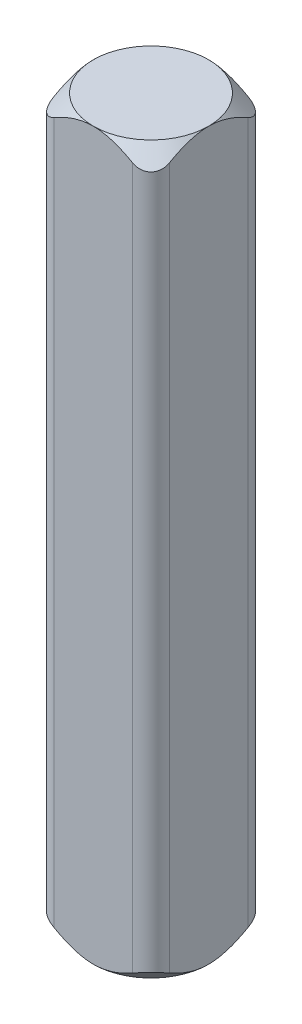
SolidWorks part; units mm, degrees
material "Plain Carbon Steel"
ref_plane "Front Plane" through (0, 0, 0) normal (0, 0, 1) x (1, 0, 0)
ref_plane "Top Plane" through (0, 0, 0) normal (0, 1, 0) x (1, 0, 0)
ref_plane "Right Plane" through (0, 0, 0) normal (1, 0, 0) x (0, 0, -1)
sketch "Sketch1" plane through (0, 0, 0) normal (0, 1, 0) x (1, 0, 0)
  line L1 (-1.5875, -1.5875) -> (1.5875, -1.5875)
  line L2 (-1.5875, -1.5875) -> (-1.5875, 1.5875)
  line L3 (-1.5875, 1.5875) -> (1.5875, 1.5875)
  line L4 (1.5875, -1.5875) -> (1.5875, 1.5875)
  line L5 (-1.5875, -1.5875) -> (1.5875, 1.5875) construction
  line L6 (-1.5875, 1.5875) -> (1.5875, -1.5875) construction
  point P0 (0, 0)
  dimension "D1" = 3.175
extrude "Boss-Extrude1" add sketch "Sketch1" along normal mid plane 20
ref_axis "a" through (0, 12.013, 0) along (0, -1, 0)
fillet "Fillet1" radius 0.508 4 edges at (-1.5875, 0, -1.5875) (-1.5875, 0, 1.5875) (1.5875, 0, -1.5875) (1.5875, 0, 1.5875)
sketch "Sketch3" plane through (0, 0, 0) normal (0, 0, 1) x (1, 0, 0)
  line L6 (0, 0) -> (0, -11.5875) construction
  line L7 (0, -11.5875) -> (1.5875, -10) construction
  line L8 (1.5875, -10) -> (2.2946, -9.2929)
  line L10 (-1.0795, -10) -> (1.0795, -10) construction
  line L11 (2.2946, -9.2929) -> (2.2946, -11)
  line L12 (2.2946, -11) -> (1.5875, -11)
  line L13 (1.5875, -10) -> (1.5875, -11)
  dimension "D1" = 45
  dimension "D2" = 1
  dimension "D3" = 1
revolve "Cut-Revolve3" cut sketch "Sketch3" angle 360 about L6
mirror "Mirror1" about plane through (0, 0, 0) normal (0, 1, 0) of "Cut-Revolve3"
equation "\"Length\"= \"Length@Boss-Extrude1\""
equation "\"Price\"= \"Length\" * 160 / ( 1m )"
